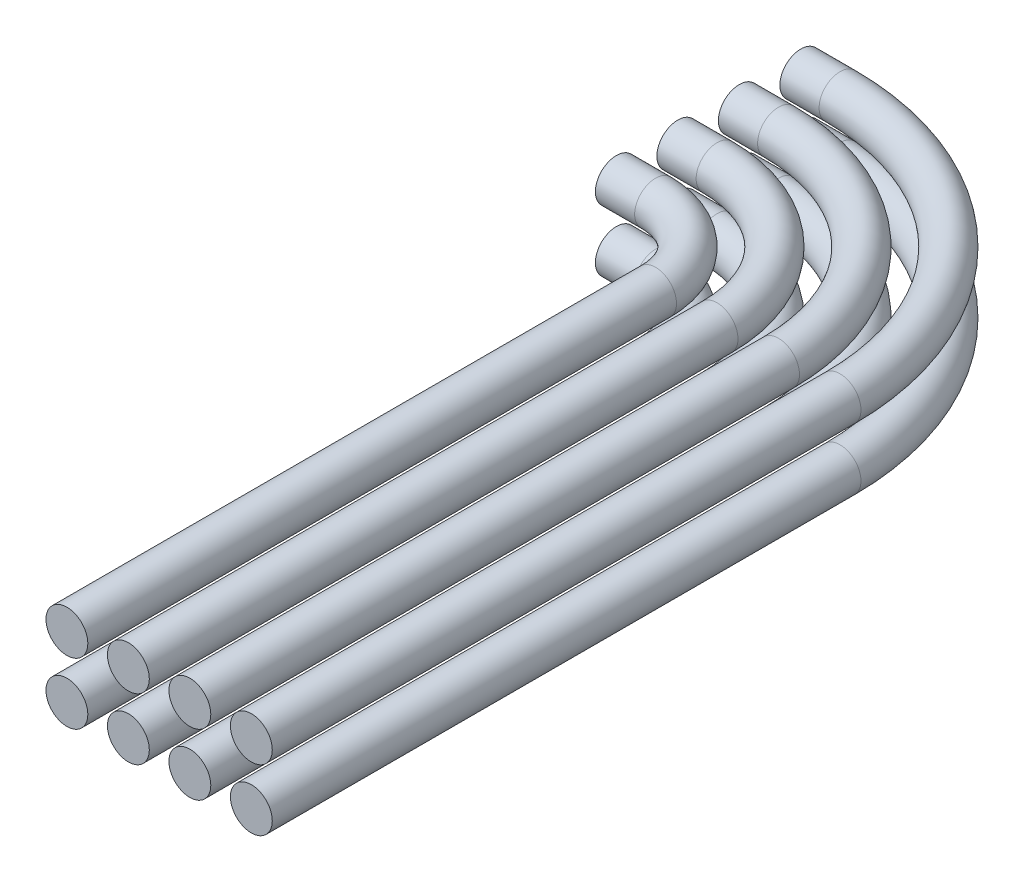
SolidWorks part; units mm, degrees
ref_plane "Front Plane" through (0, 0, 0) normal (0, 0, 1) x (1, 0, 0)
ref_plane "Top Plane" through (0, 0, 0) normal (0, 1, 0) x (1, 0, 0)
ref_plane "Right Plane" through (0, 0, 0) normal (1, 0, 0) x (0, 0, -1)
sketch "Sketch1" plane through (0, 0, 0) normal (0, 1, 0) x (1, 0, 0)
  line L0 (0, 0) -> (3, 0)
  line L1 (23, -20) -> (23, -65)
  line L2 (0, -4.7) -> (3, -4.7)
  line L3 (18.3, -20) -> (18.3, -65)
  line L4 (0, -4.7) -> (0, 0) construction
  line L5 (23, -65) -> (18.3, -65) construction
  line L6 (0, -4.7) -> (0, -9.4) construction
  line L7 (0, -9.4) -> (0, -14.1) construction
  line L8 (18.3, -65) -> (13.6, -65) construction
  line L9 (13.6, -65) -> (8.9, -65) construction
  line L10 (0, -9.4) -> (3, -9.4)
  line L11 (13.6, -20) -> (13.6, -65)
  line L12 (8.9, -65) -> (8.9, -20)
  line L13 (3, -14.1) -> (0, -14.1)
  line L14 (3, 0) -> (3, -14.1) construction
  line L15 (8.9, -20) -> (23, -20) construction
  arc A0 (3, -4.7) -> (18.3, -20) centre (3, -20) cw
  arc A1 (3, 0) -> (23, -20) centre (3, -20) cw
  arc A2 (3, -9.4) -> (13.6, -20) centre (3, -20) cw
  arc A3 (8.9, -20) -> (3, -14.1) centre (3, -20) ccw
  point P11 (23, 0)
  dimension "D5" = 20
  dimension "D1" = 4.7
  dimension "D2" = 3
  dimension "D3" = 65
ref_plane "Plane1" through (0, 0, 0) normal (1, 0, 0) x (0, 0, -1)
sketch "Sketch2" plane through (0, 0, 0) normal (1, 0, 0) x (0, 0, -1)
  circle A0 centre (0, 0) radius 1.6
  circle A1 centre (-4.7, 0) radius 1.6
  circle A2 centre (-9.4, 0) radius 1.6
  circle A3 centre (-14.1, 0) radius 1.6
  dimension "D1" = 3.2
sweep "Sweep1" add profiles "Sketch2" path "Sketch1"
sketch "Sketch3" plane through (0, 0, 0) normal (1, 0, 0) x (0, 0, -1)
  line L0 (0, 0) -> (0, 4.7) construction
  dimension "D1" = 4.7
pattern_linear "LPattern1" count 2 spacing 4.7 along (0, 1, 0) of "Sweep1"
